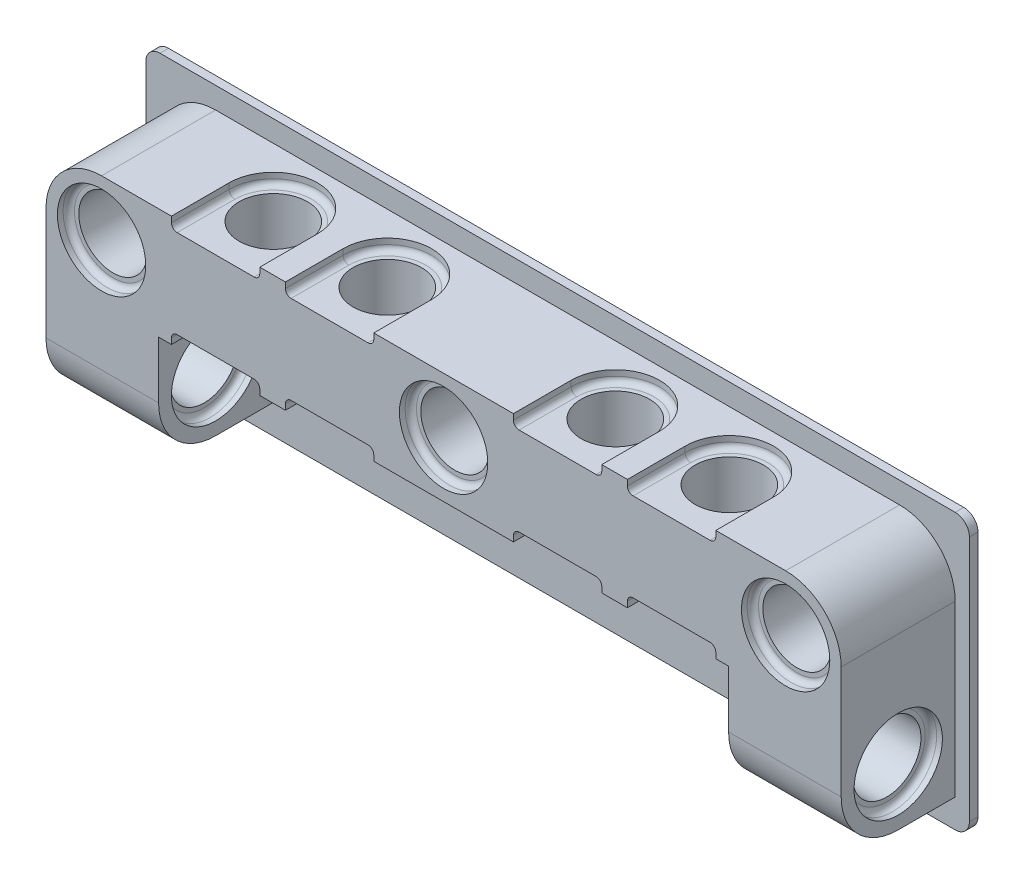
SolidWorks part; units mm, degrees
note: The reader was unsure of these and kept them because the rebuilt part matched: shared geometry of "Sketch5<3>", "Sketch6<2>", "Sketch7<2>".
material "ABS"
ref_plane "Front Plane" through (0, 0, 0) normal (0, 0, 1) x (1, 0, 0)
ref_plane "Top Plane" through (0, 0, 0) normal (0, 1, 0) x (1, 0, 0)
ref_plane "Right Plane" through (0, 0, 0) normal (1, 0, 0) x (0, 0, -1)
sketch "Sketch1" plane through (0, 0, 0) normal (0, 0, 1) x (1, 0, 0)
  line L0 (0, 3.9) -> (0, 2.4)
  line L1 (0, -3.9) -> (24, -3.9)
  line L2 (0, 3.9) -> (24, 3.9)
  line L3 (27.9, 0) -> (27.9, -3.9)
  line L4 (27.9, -3.9) -> (24, -3.9)
  line L5 (0, -3.9) -> (0, -2.4)
  circle A0 centre (24, 0) radius 3.9 construction
  arc A1 (24, 3.9) -> (27.9, 0) centre (24, 0) cw
  circle A2 centre (24, 0) radius 2.4
  arc A3 (0, 2.4) -> (0, -2.4) centre (0, 0) cw
  dimension "D3" = 4.8
  dimension "D1" = 2.4
  dimension "D2" = 7.8
extrude "Boss-Extrude1" add sketch "Sketch1" along normal blind 8
sketch "Sketch2" plane through (0, 0, 0) normal (1, 0, 0) x (0, 0, -1)
  line L0 (0, -3.9) -> (0, -11.9)
  line L1 (0, -11.9) -> (-4, -11.9)
  line L2 (-8, -3.9) -> (-8, -7.9)
  line L3 (-8, -3.9) -> (0, -3.9)
  arc A0 (-8, -7.9) -> (-4, -11.9) centre (-4, -7.9) ccw
  circle A1 centre (-4, -7.9) radius 2.4
  dimension "D3" = 4.8
  dimension "D1" = 4
  dimension "D2" = 8
extrude "Boss-Extrude2" add sketch "Sketch2" along normal up to surface (7.9 mm away) from offset 20 up to face at (27.9, -1.95, 4)
sketch "Sketch3" plane through (0, 0, 0) normal (0, 0, 1) x (1, 0, 0)
  line L0 (27.9, -11.9) -> (20, -11.9) construction
  line L1 (0, 5.4) -> (27.9, 5.4)
  line L2 (0, 5.4) -> (0, -13.9)
  line L3 (0, -13.9) -> (27.9, -13.9)
  line L4 (28.9, 4.4) -> (28.9, -12.9)
  line L5 (24, 3.9) -> (0, 3.9) construction
  line L6 (27.9, -11.9) -> (27.9, 0) construction
  arc A0 (27.9, -13.9) -> (28.9, -12.9) centre (27.9, -12.9) ccw
  arc A1 (27.9, 5.4) -> (28.9, 4.4) centre (27.9, 4.4) cw
  dimension "D4" = 1
  dimension "D1" = 2
  dimension "D2" = 1.5
  dimension "D3" = 1
extrude "Boss-Extrude3" add sketch "Sketch3" against normal blind 0.6
sketch "Sketch4" plane through (0, 0, 0) normal (0, 1, 0) x (1, 0, 0)
  line L0 (24, 0) -> (0, 0) construction
  line L1 (0, -8) -> (0, 0) construction
  circle A0 centre (8, -3.95) radius 2.4
  circle A1 centre (16, -3.95) radius 2.4
  dimension "D1" = 8
  dimension "D4" = 4.8
  dimension "D2" = 3.95
  dimension "D3" = 8
extrude "Cut-Extrude1" cut sketch "Sketch4" against normal through all both and the other way through all
sketch "Sketch5" plane through (0, 0, 0) normal (0, 1, 0) x (1, 0, 0)
  line L0 (4.9, -3.95) -> (4.9, -10.0471)
  line L1 (4.9, -10.0471) -> (11.1, -10.0471)
  line L2 (11.1, -10.0471) -> (11.1, -3.95)
  line L3 (12.9, -3.95) -> (12.9, -10.0471)
  line L4 (12.9, -10.0471) -> (19.1, -10.0471)
  line L5 (19.1, -10.0471) -> (19.1, -3.95)
  circle A0 centre (8, -3.95) radius 3.1
  circle A1 centre (16, -3.95) radius 3.1
  dimension "D1" = 6.2
extrude "Cut-Extrude2" cut sketch "Sketch5" against normal blind 0.8 from vertex contours A0 L0 L1 L2 | A0 | A1 L3 L4 L5 | A1
extrude "Cut-Extrude3" cut sketch "Sketch5<3>" along normal blind 0.8 from vertex contours A0 | A0 L0 L1 L2 | A1 | A1 L3 L4 L5
sketch "Sketch5<3>" plane through (0, 0, 0) normal (0, 1, 0) x (1, 0, 0) same geometry as "Sketch5"
sketch "Sketch6" plane through (0, 0, 0) normal (1, 0, 0) x (0, 0, -1)
  circle A0 centre (-4, -7.9) radius 3.1
  dimension "D1" = 6.2
extrude "Cut-Extrude4" cut sketch "Sketch6" against normal blind 0.8 from surface at 27.9 starting at face at (27.9, -6.5057, 4.1657)
extrude "Cut-Extrude5" cut sketch "Sketch6<2>" along normal blind 0.8 from surface at 20 starting at face at (20, -8.0657, 4.1657)
sketch "Sketch6<2>" plane through (0, 0, 0) normal (1, 0, 0) x (0, 0, -1) same geometry as "Sketch6"
sketch "Sketch7" plane through (0, 0, 0) normal (0, 0, 1) x (1, 0, 0)
  line L0 (0, 2.4) -> (0, -2.4) construction
  line L1 (0, 3.1) -> (0, -3.1)
  circle A0 centre (24, 0) radius 3.1
  arc A1 (0, 3.1) -> (0, -3.1) centre (0, 0) cw
  dimension "D1" = 6.2
extrude "Cut-Extrude6" cut sketch "Sketch7" against normal through all from offset 0.8
extrude "Cut-Extrude7" cut sketch "Sketch7<2>" against normal blind 0.8 from vertex
sketch "Sketch7<2>" plane through (0, 0, 0) normal (0, 0, 1) x (1, 0, 0) same geometry as "Sketch7"
fillet "Fillet1" radius 0.4 18 edges at (11.1, -3.1, 5.975) (4.9, -3.1, 5.975) (19.1, -3.1, 5.975) (12.9, -3.1, 5.975) (4.9, 3.1, 5.975) (8, 3.1, 0.85) (12.9, 3.1, 5.975) (16, 3.1, 0.85) (8, -3.1, 0.85) (16, -3.1, 0.85) (11.1, 3.1, 5.975) (19.1, 3.1, 5.975) (3.1, 0, 0.8) (27.1, 0, 0.8) (27.1, -7.9, 7.1) (20.8, -7.9, 0.9) (27.1, 0, 7.2) (3.1, 0, 7.2)
mirror "Mirror1" about plane through (0, 0, 0) normal (1, 0, 0) of bodies 111 104
equation "\"HoleSize\"= 4.8mm"
equation "\"D3@Sketch2\"=\"HoleSize\""
equation "\"D3@Sketch1\"=\"HoleSize\""
equation "\"D1@Sketch1\"=\"HoleSize\"/2"
equation "\"BigHole\"= 6.2mm"
equation "\"D1@Sketch5\"=\"BigHole\""
equation "\"D1@Sketch6\"=\"BigHole\""
equation "\"D1@Sketch7\"=\"BigHole\""
